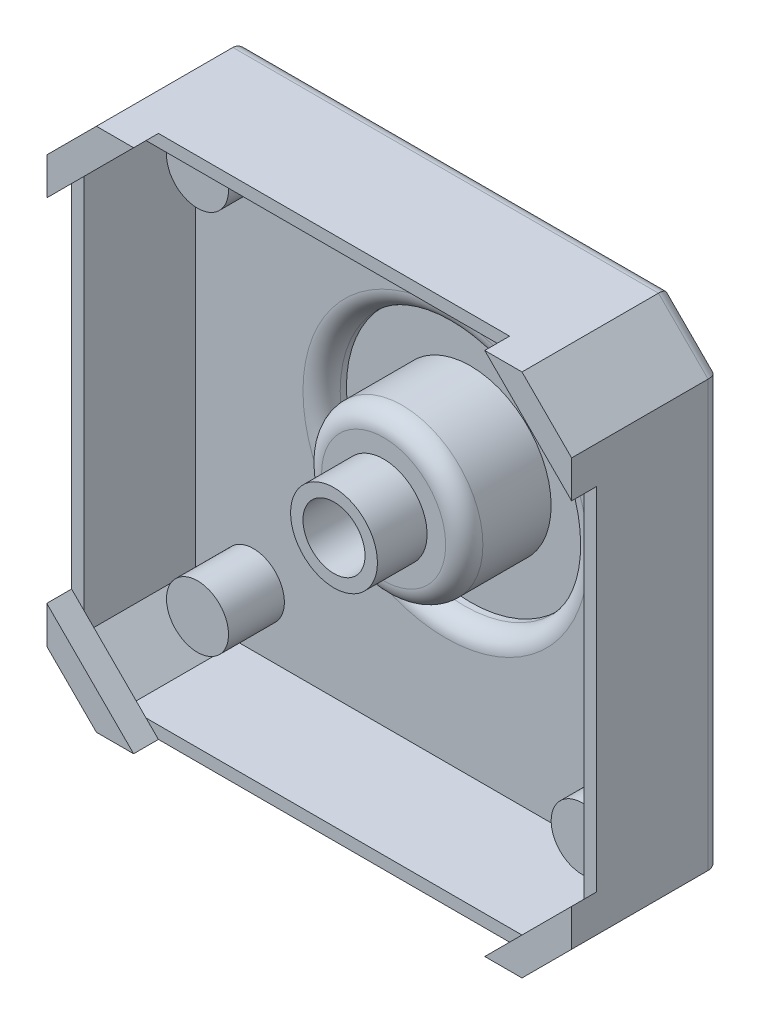
SolidWorks part; units mm, degrees
material "Plain Carbon Steel"
ref_plane "Alzado" through (0, 0, 0) normal (0, 0, 1) x (1, 0, 0)
ref_plane "Planta" through (0, 0, 0) normal (0, 1, 0) x (1, 0, 0)
ref_plane "Vista lateral" through (0, 0, 0) normal (1, 0, 0) x (0, 0, -1)
sketch "Croquis1" plane through (0, 0, 0) normal (0, 0, 1) x (1, 0, 0)
  line L0 (-21.15, 17.15) -> (-17.15, 21.15)
  line L1 (-17.15, 21.15) -> (17.15, 21.15)
  line L2 (-21.15, 17.15) -> (-21.15, -17.15)
  line L3 (-17.15, -21.15) -> (17.15, -21.15)
  line L4 (21.15, 17.15) -> (21.15, -17.15)
  line L5 (-21.15, 21.15) -> (21.15, -21.15) construction
  line L6 (-21.15, -21.15) -> (21.15, 21.15) construction
  line L7 (-21.15, -17.15) -> (-17.15, -21.15)
  line L8 (17.15, -21.15) -> (21.15, -17.15)
  line L9 (17.15, 21.15) -> (21.15, 17.15)
  point P0 (0, 0)
  dimension "D1" = 42.3
  dimension "D2" = 42.3
extrude "Saliente-Extruir1" add sketch "Croquis1" along normal blind 12
sketch "Croquis2" plane through (0, 0, 12) normal (0, 0, 1) x (1, 0, 0)
  line L0 (-14.15, 21.15) -> (-21.15, 14.15)
  line L1 (-14.15, 21.15) -> (14.15, 21.15)
  line L2 (-21.15, 14.15) -> (-21.15, -14.15)
  line L3 (-14.15, -21.15) -> (14.15, -21.15)
  line L4 (21.15, 14.15) -> (21.15, -14.15)
  line L5 (-21.15, 21.15) -> (21.15, -21.15) construction
  line L6 (-21.15, -21.15) -> (21.15, 21.15) construction
  line L7 (14.15, 21.15) -> (21.15, 14.15)
  line L8 (21.15, -14.15) -> (14.15, -21.15)
  line L9 (-21.15, -14.15) -> (-14.15, -21.15)
  point P0 (0, 0)
  dimension "D1" = 42.3
  dimension "D2" = 42.3
extrude "Cortar-Extruir1" cut sketch "Croquis2" against normal blind 2
sketch "Croquis3" plane through (0, 0, 0) normal (0, 0, -1) x (-1, 0, 0)
  circle A0 centre (0, 0) radius 11
  dimension "D1" = 22
extrude "Saliente-Extruir2" add sketch "Croquis3" along normal blind 2
sketch "Croquis4" plane through (0, 0, -2) normal (0, 0, -1) x (-1, 0, 0)
  circle A0 centre (0, 0) radius 5.5
  dimension "D1" = 11
extrude "Cortar-Extruir2" cut sketch "Croquis4" against normal blind 7
sketch "Croquis5" plane through (0, 0, 5) normal (0, 0, -1) x (-1, 0, 0)
  circle A0 centre (0, 0) radius 2.5
  dimension "D1" = 5
extrude "Cortar-Extruir3" cut sketch "Croquis5" against normal blind 7
fillet "Redondeo2" radius 1 8 edges at (19.15, -19.15, 0) (-19.15, -19.15, 0) (0, -21.15, 0) (-21.15, 0, 0) (-19.15, 19.15, 0) (0, 21.15, 0) (19.15, 19.15, 0) (21.15, 0, 0)
fillet "Redondeo3" radius 0.5 4 edges at (-5.5, 0, -2) (-5.5, 0, 5) (-11, 0, 0) (-11, 0, -2)
sketch "Croquis6" plane through (0, 0, 0) normal (0, 0, -1) x (-1, 0, 0)
  line L1 (15.5, -15.5) -> (-15.5, -15.5) construction
  line L2 (15.5, -15.5) -> (15.5, 15.5) construction
  line L3 (15.5, 15.5) -> (-15.5, 15.5) construction
  line L4 (-15.5, -15.5) -> (-15.5, 15.5) construction
  line L5 (15.5, -15.5) -> (-15.5, 15.5) construction
  line L6 (15.5, 15.5) -> (-15.5, -15.5) construction
  circle A0 centre (-15.5, 15.5) radius 1.5
  circle A1 centre (15.5, 15.5) radius 1.5
  circle A2 centre (15.5, -15.5) radius 1.5
  circle A3 centre (-15.5, -15.5) radius 1.5
  circle A4 centre (0, 0) radius 21.9203 construction
  point P12 (0, 0)
  dimension "D1" = 3
  dimension "D2" = 31
  dimension "D4" = 4
extrude "Cortar-Extruir4" cut sketch "Croquis6" against normal blind 4.5
fillet "Redondeo4" radius 0.5 4 edges at (14, -15.5, 0) (-17, -15.5, 0) (-17, 15.5, 0) (14, 15.5, 0)
shell "Shell1" thickness 1 removed face at (2.5, 0, 10)
